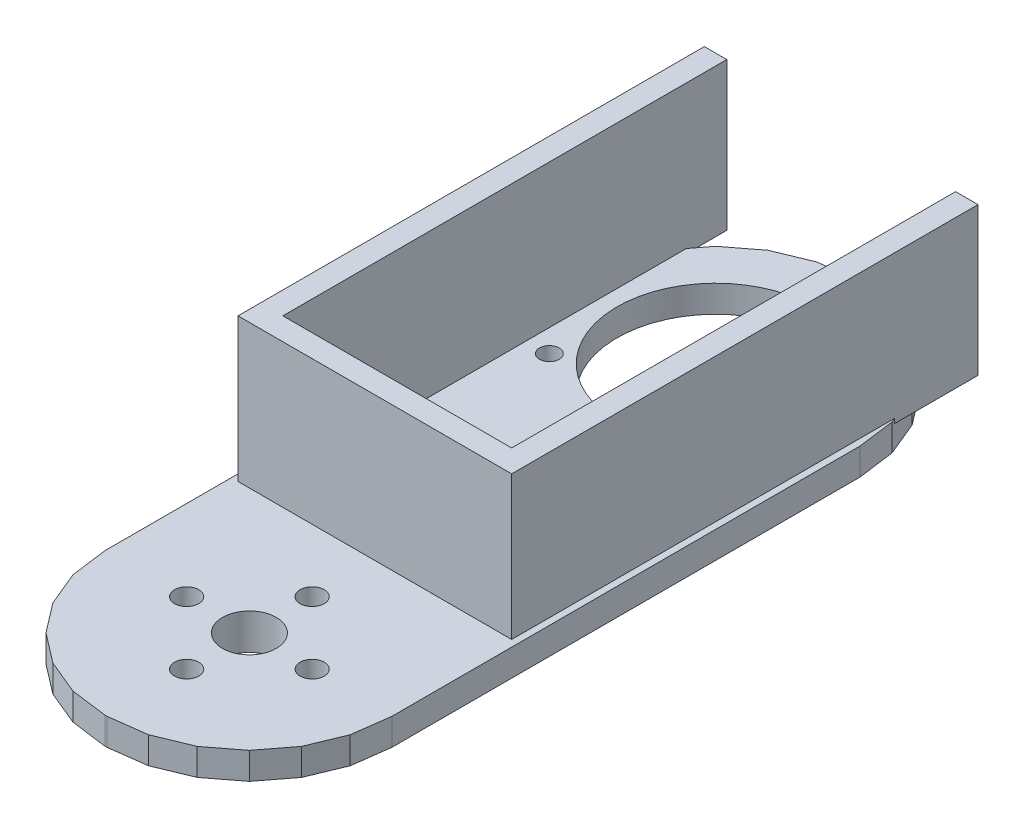
SolidWorks part; units mm, degrees
ref_plane "Front Plane" through (0, 0, 0) normal (0, 0, 1) x (1, 0, 0)
ref_plane "Top Plane" through (0, 0, 0) normal (0, 1, 0) x (1, 0, 0)
ref_plane "Right Plane" through (0, 0, 0) normal (1, 0, 0) x (0, 0, -1)
sketch "S_cyl1" plane through (0, 0, 0) normal (0, 1, 0) x (1, 0, 0)
  circle A0 centre (0, 0) radius 11
  dimension "D1_S_cyl1" = 22
extrude "Boss_1" add sketch "S_cyl1" along normal blind 1.1
ref_plane "PY_p1_000" through (0, 1, 0) normal (0, 1, 0) x (1, 0, 0)
sketch "S_prism2" plane through (0, 1, 0) normal (0, 1, 0) x (1, 0, 0)
  line L0 (-16, -0.1) -> (-15.458, -4.215)
  line L1 (-15.458, -4.215) -> (-13.87, -8.05)
  line L2 (-13.87, -8.05) -> (-11.343, -11.343)
  line L3 (-11.343, -11.343) -> (-8.05, -13.87)
  line L4 (-8.05, -13.87) -> (-4.215, -15.458)
  line L5 (-4.215, -15.458) -> (-0.1, -16)
  line L6 (-0.1, -16) -> (0.1, -16)
  line L7 (0.1, -16) -> (4.215, -15.458)
  line L8 (4.215, -15.458) -> (8.05, -13.87)
  line L9 (8.05, -13.87) -> (11.343, -11.343)
  line L10 (11.343, -11.343) -> (13.87, -8.05)
  line L11 (13.87, -8.05) -> (15.458, -4.215)
  line L12 (15.458, -4.215) -> (16, -0.1)
  line L13 (16, -0.1) -> (16, 52.1)
  line L14 (16, 52.1) -> (15.458, 56.215)
  line L15 (15.458, 56.215) -> (13.87, 60.05)
  line L16 (13.87, 60.05) -> (11.343, 63.343)
  line L17 (11.343, 63.343) -> (8.05, 65.87)
  line L18 (8.05, 65.87) -> (4.215, 67.458)
  line L19 (4.215, 67.458) -> (0.1, 68)
  line L20 (0.1, 68) -> (-0.1, 68)
  line L21 (-0.1, 68) -> (-4.215, 67.458)
  line L22 (-4.215, 67.458) -> (-8.05, 65.87)
  line L23 (-8.05, 65.87) -> (-11.343, 63.343)
  line L24 (-11.343, 63.343) -> (-13.87, 60.05)
  line L25 (-13.87, 60.05) -> (-15.458, 56.215)
  line L26 (-15.458, 56.215) -> (-16, 52.1)
  line L27 (-16, 52.1) -> (-16, -0.1)
  dimension "P1" = 16
  dimension "P2" = 0.1
  dimension "P3" = 15.458
  dimension "P4" = 4.215
  dimension "P5" = 13.87
  dimension "P6" = 8.05
  dimension "P7" = 11.343
  dimension "P8" = 11.343
  dimension "P9" = 8.05
  dimension "P10" = 13.87
  dimension "P11" = 4.215
  dimension "P12" = 15.458
  dimension "P13" = 0.1
  dimension "P14" = 16
  dimension "P15" = 0.1
  dimension "P16" = 16
  dimension "P17" = 4.215
  dimension "P18" = 15.458
  dimension "P19" = 8.05
  dimension "P20" = 13.87
  dimension "P21" = 11.343
  dimension "P22" = 11.343
  dimension "P23" = 13.87
  dimension "P24" = 8.05
  dimension "P25" = 15.458
  dimension "P26" = 4.215
  dimension "P27" = 16
  dimension "P28" = 0.1
  dimension "P29" = 16
  dimension "P30" = 52.1
  dimension "P31" = 15.458
  dimension "P32" = 56.215
  dimension "P33" = 13.87
  dimension "P34" = 60.05
  dimension "P35" = 11.343
  dimension "P36" = 63.343
  dimension "P37" = 8.05
  dimension "P38" = 65.87
  dimension "P39" = 4.215
  dimension "P40" = 67.458
  dimension "P41" = 0.1
  dimension "P42" = 68
  dimension "P43" = 0.1
  dimension "P44" = 68
  dimension "P45" = 4.215
  dimension "P46" = 67.458
  dimension "P47" = 8.05
  dimension "P48" = 65.87
  dimension "P49" = 11.343
  dimension "P50" = 63.343
  dimension "P51" = 13.87
  dimension "P52" = 60.05
  dimension "P53" = 15.458
  dimension "P54" = 56.215
  dimension "P55" = 16
  dimension "P56" = 52.1
extrude "Boss_2" add sketch "S_prism2" along normal blind 3
ref_plane "PZ_m66_000" through (0, 0, -66) normal (0, 0, 1) x (1, 0, 0)
sketch "S_box3" plane through (0, 0, -66) normal (0, 0, 1) x (1, 0, 0)
  line L0 (12.76, 3.5) -> (15.26, 3.5)
  line L1 (15.26, 3.5) -> (15.26, 20)
  line L2 (15.26, 20) -> (12.76, 20)
  line L3 (12.76, 20) -> (12.76, 3.5)
  dimension "P1" = 12.76
  dimension "P2" = 3.5
  dimension "P3" = 15.26
  dimension "P4" = 3.5
  dimension "P5" = 15.26
  dimension "P6" = 20
  dimension "P7" = 12.76
  dimension "P8" = 20
extrude "Boss_3" add sketch "S_box3" along normal blind 52.01
sketch "S_box4" plane through (0, 0, -66) normal (0, 0, 1) x (1, 0, 0)
  line L0 (-15.26, 3.5) -> (-12.76, 3.5)
  line L1 (-12.76, 3.5) -> (-12.76, 20)
  line L2 (-12.76, 20) -> (-15.26, 20)
  line L3 (-15.26, 20) -> (-15.26, 3.5)
  dimension "P1" = 15.26
  dimension "P2" = 3.5
  dimension "P3" = 12.76
  dimension "P4" = 3.5
  dimension "P5" = 12.76
  dimension "P6" = 20
  dimension "P7" = 15.26
  dimension "P8" = 20
extrude "Boss_4" add sketch "S_box4" along normal blind 52.01
ref_plane "PZ_m16_490" through (0, 0, -16.49) normal (0, 0, 1) x (1, 0, 0)
sketch "S_box5" plane through (0, 0, -16.49) normal (0, 0, 1) x (1, 0, 0)
  line L0 (-15.26, 3.5) -> (15.26, 3.5)
  line L1 (15.26, 3.5) -> (15.26, 20)
  line L2 (15.26, 20) -> (-15.26, 20)
  line L3 (-15.26, 20) -> (-15.26, 3.5)
  dimension "P1" = 15.26
  dimension "P2" = 3.5
  dimension "P3" = 15.26
  dimension "P4" = 3.5
  dimension "P5" = 15.26
  dimension "P6" = 20
  dimension "P7" = 15.26
  dimension "P8" = 20
extrude "Boss_5" add sketch "S_box5" along normal blind 2.5
ref_plane "PY_m0_100" through (0, -0.1, 0) normal (0, 1, 0) x (1, 0, 0)
sketch "S_hole6" plane through (0, -0.1, 0) normal (0, 1, 0) x (1, 0, 0)
  circle A0 centre (0, 0) radius 3
  dimension "D1_S_hole6" = 6
extrude "Hole_6" cut sketch "S_hole6" along normal blind 4.2
sketch "S_hole7" plane through (0, -0.1, 0) normal (0, 1, 0) x (1, 0, 0)
  circle A0 centre (7, 0) radius 1.35
  dimension "D1_S_hole7" = 2.7
  dimension "P2" = 7
extrude "Hole_7" cut sketch "S_hole7" along normal blind 4.2
sketch "S_hole8" plane through (0, -0.1, 0) normal (0, 1, 0) x (1, 0, 0)
  circle A0 centre (0, -7) radius 1.35
  dimension "D1_S_hole8" = 2.7
  dimension "P2" = 7
extrude "Hole_8" cut sketch "S_hole8" along normal blind 4.2
sketch "S_hole9" plane through (0, -0.1, 0) normal (0, 1, 0) x (1, 0, 0)
  circle A0 centre (-7, 0) radius 1.35
  dimension "D1_S_hole9" = 2.7
  dimension "P2" = 7
extrude "Hole_9" cut sketch "S_hole9" along normal blind 4.2
sketch "S_hole10" plane through (0, -0.1, 0) normal (0, 1, 0) x (1, 0, 0)
  circle A0 centre (0, 7) radius 1.35
  dimension "D1_S_hole10" = 2.7
  dimension "P2" = 7
extrude "Hole_10" cut sketch "S_hole10" along normal blind 4.2
ref_plane "PY_p0_900" through (0, 0.9, 0) normal (0, 1, 0) x (1, 0, 0)
sketch "S_hole11" plane through (0, 0.9, 0) normal (0, 1, 0) x (1, 0, 0)
  circle A0 centre (0, 52) radius 11
  dimension "D1_S_hole11" = 22
  dimension "P2" = 52
extrude "Hole_11" cut sketch "S_hole11" along normal blind 3.2
sketch "S_hole12" plane through (0, 0.9, 0) normal (0, 1, 0) x (1, 0, 0)
  circle A0 centre (-10.25, 43.7) radius 1.1
  dimension "D1_S_hole12" = 2.2
  dimension "P2" = 10.25
  dimension "P3" = 43.7
extrude "Hole_12" cut sketch "S_hole12" along normal blind 3.2
sketch "S_hole13" plane through (0, 0.9, 0) normal (0, 1, 0) x (1, 0, 0)
  circle A0 centre (10.25, 43.7) radius 1.1
  dimension "D1_S_hole13" = 2.2
  dimension "P2" = 10.25
  dimension "P3" = 43.7
extrude "Hole_13" cut sketch "S_hole13" along normal blind 3.2
sketch "S_hole14" plane through (0, 0.9, 0) normal (0, 1, 0) x (1, 0, 0)
  circle A0 centre (-10.25, 19.25) radius 1.1
  dimension "D1_S_hole14" = 2.2
  dimension "P2" = 10.25
  dimension "P3" = 19.25
extrude "Hole_14" cut sketch "S_hole14" along normal blind 3.2
sketch "S_hole15" plane through (0, 0.9, 0) normal (0, 1, 0) x (1, 0, 0)
  circle A0 centre (10.25, 19.25) radius 1.1
  dimension "D1_S_hole15" = 2.2
  dimension "P2" = 10.25
  dimension "P3" = 19.25
extrude "Hole_15" cut sketch "S_hole15" along normal blind 3.2
equation "\"plate_t\" = 3"
equation "\"clearance\" = 0.4"
